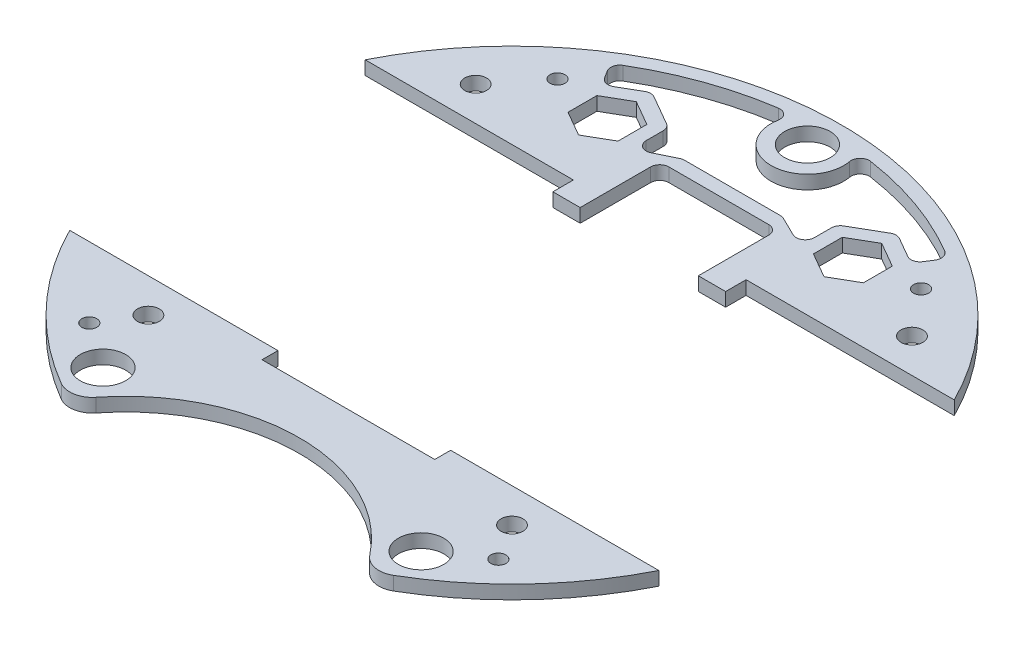
SolidWorks part; units mm, degrees
material "Acrylic (Medium-high impact)"
ref_plane "Front Plane" through (0, 0, 0) normal (0, 0, 1) x (1, 0, 0)
ref_plane "Top Plane" through (0, 0, 0) normal (0, 1, 0) x (1, 0, 0)
ref_plane "Right Plane" through (0, 0, 0) normal (1, 0, 0) x (0, 0, -1)
sketch "Sketch1" plane through (0, 0, 0) normal (0, 1, 0) x (1, 0, 0)
  line L0 (0, -85) -> (-32.4891, -64.8129) construction
  line L1 (0, -85) -> (0, 0) construction
  arc A0 (36.5434, -62.6165) -> (-36.5434, -62.6165) centre (0, 0) ccw
  arc A1 (30.0898, -61.3851) -> (-30.0898, -61.3851) centre (0, -85) ccw
  arc A2 (-30.0898, -61.3851) -> (-36.5434, -62.6165) centre (-34.0231, -58.2982) cw
  arc A3 (36.5434, -62.6165) -> (30.0898, -61.3851) centre (34.0231, -58.2982) cw
  dimension "D1" = 145
  dimension "D2" = 76.5
  dimension "D4" = 5
  dimension "D3" = 85
extrude "Boss-Extrude1" add sketch "Sketch1" along normal blind 3
sketch "solenoid placement" plane through (0, 3, 0) normal (0, 1, 0) x (1, 0, 0)
  line L4 (-19, -36) -> (19, -36)
  line L5 (-19, 28) -> (-19, -36)
  line L6 (19, 28) -> (-19, 28)
  line L7 (19, -36) -> (19, 28)
  line L8 (-19, -36) -> (19, -36)
  line L9 (-19, 28) -> (-19, -36)
  line L10 (19, 28) -> (-19, 28)
  line L11 (19, -36) -> (19, 28)
  dimension "D1" = 0
extrude "Cut-Extrude1" cut sketch "solenoid placement" against normal through all
sketch "Sketch4" plane through (0, 3, 0) normal (0, 1, 0) x (1, 0, 0)
  line L8 (13, 28) -> (13, 43.5)
  line L9 (-13, 28) -> (13, 28)
  line L10 (-13, 43.5) -> (-13, 28)
  line L11 (11, 45.5) -> (-11, 45.5)
  line L28 (13, 28) -> (13, 43.5)
  line L29 (-13, 28) -> (13, 28)
  line L30 (-13, 43.5) -> (-13, 28)
  line L31 (11, 45.5) -> (-11, 45.5)
  arc A4 (-11, 45.5) -> (-13, 43.5) centre (-11, 43.5) ccw
  arc A5 (13, 43.5) -> (11, 45.5) centre (11, 43.5) ccw
  arc A14 (-11, 45.5) -> (-13, 43.5) centre (-11, 43.5) ccw
  arc A15 (13, 43.5) -> (11, 45.5) centre (11, 43.5) ccw
  dimension "D1" = 0
extrude "Cut-Extrude4" cut sketch "Sketch4" against normal through all
sketch "Sketch5" plane through (0, 3, 0) normal (0, 1, 0) x (1, 0, 0)
  line L12 (-21.5, 51.1754) -> (-27, 54.3509)
  line L13 (-27, 54.3509) -> (-32.5, 51.1754)
  line L14 (-32.5, 51.1754) -> (-32.5, 44.8246)
  line L15 (-32.5, 44.8246) -> (-27, 41.6491)
  line L16 (-27, 41.6491) -> (-21.5, 44.8246)
  line L17 (-21.5, 44.8246) -> (-21.5, 51.1754)
  line L18 (-21.5, 51.1754) -> (-27, 54.3509)
  line L19 (-27, 54.3509) -> (-32.5, 51.1754)
  line L20 (-32.5, 51.1754) -> (-32.5, 44.8246)
  line L21 (-32.5, 44.8246) -> (-27, 41.6491)
  line L22 (-27, 41.6491) -> (-21.5, 44.8246)
  line L23 (-21.5, 44.8246) -> (-21.5, 51.1754)
  line L24 (21.5, 51.1754) -> (21.5, 44.8246)
  line L25 (21.5, 44.8246) -> (27, 41.6491)
  line L26 (27, 41.6491) -> (32.5, 44.8246)
  line L27 (32.5, 44.8246) -> (32.5, 51.1754)
  line L28 (32.5, 51.1754) -> (27, 54.3509)
  line L29 (27, 54.3509) -> (21.5, 51.1754)
  line L42 (21.5, 51.1754) -> (21.5, 44.8246)
  line L43 (21.5, 44.8246) -> (27, 41.6491)
  line L44 (27, 41.6491) -> (32.5, 44.8246)
  line L45 (32.5, 44.8246) -> (32.5, 51.1754)
  line L46 (32.5, 51.1754) -> (27, 54.3509)
  line L47 (27, 54.3509) -> (21.5, 51.1754)
  dimension "D1" = 0
  dimension "D2" = 0
extrude "Cut-Extrude5" cut sketch "Sketch5" against normal through all
sketch "Sketch6" plane through (0, 3, 0) normal (0, 1, 0) x (1, 0, 0)
  circle A1 centre (40, -40) radius 2.4
  circle A2 centre (40, -40) radius 2.4
  circle A3 centre (-40, -40) radius 2.4
  circle A4 centre (-40, -40) radius 2.4
  circle A5 centre (48, 40) radius 2.4
  circle A6 centre (48, 40) radius 2.4
  circle A7 centre (-48, 40) radius 2.4
  circle A8 centre (-48, 40) radius 2.4
  dimension "D1" = 0
  dimension "D2" = 0
  dimension "D3" = 0
  dimension "D4" = 0
extrude "Cut-Extrude6" cut sketch "Sketch6" against normal through all
sketch "Sketch3" plane through (0, 3, 0) normal (0, 1, 0) x (1, 0, 0)
  line L0 (-19, 28) -> (-19, 32.5)
  line L1 (72.5, -32.5) -> (-72.5, -32.5)
  line L2 (72.5, -32.5) -> (72.5, 32.5)
  line L3 (72.5, 32.5) -> (19, 32.5)
  line L4 (-72.5, -32.5) -> (-72.5, 32.5)
  line L5 (72.5, -32.5) -> (-72.5, 32.5) construction
  line L6 (72.5, 32.5) -> (-72.5, -32.5) construction
  line L7 (-19, 28) -> (19, 28)
  line L8 (19, 28) -> (19, 32.5)
  line L9 (-19, 32.5) -> (-72.5, 32.5)
  line L10 (-19, 28) -> (-19, -36) construction
  line L11 (-13, 28) -> (-19, 28) construction
  arc A0 (36.5434, -62.6165) -> (-36.5434, -62.6165) centre (0, 0) ccw construction
  point P0 (0, 0)
  dimension "D1" = 65
extrude "Cut-Extrude3" cut sketch "Sketch3" against normal through all
sketch "Sketch7" plane through (0, 3, 0) normal (0, 1, 0) x (1, 0, 0)
  circle A1 centre (35, -55) radius 5
  circle A2 centre (35, -55) radius 5
  circle A3 centre (-35, -55) radius 5
  circle A4 centre (-35, -55) radius 5
  dimension "D1" = 0
  dimension "D2" = 0
extrude "Cut-Extrude7" cut sketch "Sketch7" against normal through all
sketch "Sketch8" plane through (0, 3, 0) normal (0, -1, 0) x (1, 0, 0)
  circle A1 centre (0, -65) radius 5
  circle A2 centre (0, -65) radius 5
  dimension "D1" = 0
extrude "Cut-Extrude9" cut sketch "Sketch8" along normal through all
sketch "Sketch9" plane through (0, 3, 0) normal (0, 1, 0) x (1, 0, 0)
  line L0 (0, 0) -> (0, -21.5516) construction
  circle A0 centre (45, -48) radius 1.65
  circle A1 centre (-45, -48) radius 1.65
  circle A2 centre (40, 50) radius 1.65
  circle A3 centre (-40, 50) radius 1.65
  dimension "D3" = 3.3
  dimension "D1" = 45
  dimension "D2" = 48
  dimension "D4" = 40
  dimension "D5" = 50
extrude "Cut-Extrude10" cut sketch "Sketch9" against normal through all
sketch "Sketch10" plane through (0, 0, 0) normal (0, -1, 0) x (1, 0, 0)
  line L21 (-18.5, -44.8246) -> (-18.5, -52.9075)
  line L22 (-18.5, -52.9075) -> (-27, -57.815)
  line L23 (-27, -57.815) -> (-34, -53.7735)
  line L24 (-18.5, -48.0319) -> (-18.5, -51.7528)
  line L25 (-19.5, -53.4848) -> (-26, -57.2376)
  line L26 (-28, -57.2376) -> (-32.3362, -54.7341)
  line L31 (15.6199, -46.236) -> (11.4164, -48.2959)
  line L32 (11, -48.5) -> (-11, -48.5)
  line L33 (34, -53.7735) -> (27, -57.815)
  line L34 (27, -57.815) -> (18.5, -52.9075)
  line L35 (18.5, -52.9075) -> (18.5, -44.8246)
  line L36 (32.3362, -54.7341) -> (28, -57.2376)
  line L37 (26, -57.2376) -> (19.5, -53.4848)
  line L38 (18.5, -51.7528) -> (18.5, -48.0319)
  line L39 (10.5363, -48.5) -> (-10.5363, -48.5)
  line L40 (35.0267, -55.3973) -> (36.0573, -57.0273)
  line L41 (-11.4164, -48.2959) -> (-15.6199, -46.236)
  line L42 (-35.0267, -55.3973) -> (-36.0573, -57.0273)
  arc A21 (-62.1257, -31.1552) -> (62.1257, -31.1552) centre (0, 0) ccw
  arc A22 (-35.3852, -59.8175) -> (-10.1321, -68.7575) centre (0, 0) ccw
  arc A23 (10.1321, -68.7575) -> (35.3852, -59.8175) centre (0, 0) ccw
  circle A24 centre (0, -65) radius 8
  arc A25 (7.8724, -66.4231) -> (-7.8724, -66.4231) centre (0, -65) ccw
  arc A26 (-7.8724, -66.4231) -> (-10.1321, -68.7575) centre (-9.8405, -66.7788) cw
  arc A27 (7.8724, -66.4231) -> (10.1321, -68.7575) centre (9.8405, -66.7788) ccw
  arc A28 (36.0573, -57.0273) -> (35.3852, -59.8175) centre (34.3669, -58.0962) cw
  arc A29 (32.3362, -54.7341) -> (35.0267, -55.3973) centre (33.3362, -56.4661) cw
  arc A30 (28, -57.2376) -> (26, -57.2376) centre (27, -55.5056) cw
  arc A31 (19.5, -53.4848) -> (18.5, -51.7528) centre (20.5, -51.7528) cw
  arc A32 (18.5, -48.0319) -> (15.6199, -46.236) centre (16.5, -48.0319) ccw
  arc A33 (10.5363, -48.5) -> (11.4164, -48.2959) centre (10.5363, -46.5) ccw
  arc A34 (-10.5363, -48.5) -> (-11.4164, -48.2959) centre (-10.5363, -46.5) cw
  arc A35 (-18.5, -48.0319) -> (-15.6199, -46.236) centre (-16.5, -48.0319) cw
  arc A36 (-18.5, -51.7528) -> (-19.5, -53.4848) centre (-20.5, -51.7528) cw
  arc A37 (-26, -57.2376) -> (-28, -57.2376) centre (-27, -55.5056) cw
  arc A38 (-32.3362, -54.7341) -> (-35.0267, -55.3973) centre (-33.3362, -56.4661) ccw
  arc A39 (-36.0573, -57.0273) -> (-35.3852, -59.8175) centre (-34.3669, -58.0962) ccw
  point P23 (6.8312, -69.1635)
  dimension "D6" = 2
  dimension "D1" = 3
  dimension "D2" = 3
  dimension "D3" = 3
  dimension "D4" = 3
  dimension "D5" = 3
extrude "Cut-Extrude12" cut sketch "Sketch10" against normal through all contours L42 A39 A22 A26 A25 A27 A23 A28 L40 A29 L36 A30 L37 A31 L38 A32 L31 A33 L39 A34 L41 A35 L24 A36 L25 A37 L26 A38 region at (-17.155, 0, -46.9815) region at (-18.7098, 0, -52.7863) region at (-27, 0, -57.5727) region at (18.7098, 0, -52.7863) region at (27, 0, -57.5727)
equation "\"smallPulleyTeeth\"= 30"
equation "\"largePulleyTeeth\"= 30"
equation "\"eighthThick\"= 3.0mm"
equation "\"sixteenthThick\" = 1.7mm"
equation "\"quarterThick\"=6.0mm"
equation "\"OD\" = 145mm"
equation "\"puckAngle\" = 60.5deg"
equation "\"D1@Sketch1\"=\"OD\""
equation "\"puckDiam\" = 76.5mm"
equation "\"D2@Sketch1\"=\"puckDiam\""
equation "\"D1@Boss-Extrude1\"=\"eighthThick\""
equation "\"axlePress\" = 5.9mm"
equation "\"press\" = 0.2mm"
equation "\"wheelClear\" = 0.3mm"
equation "\"10-32clear\" = 4.8mm"
equation "\"6-32clear\" = 3.3mm"
equation "\"8-32clear\" = 4.0mm"
equation "\"wheelHeight\" = 22mm"
equation "\"wheelWell\" = 65mm"
equation "\"D1@Sketch3\"=\"wheelWell\""
equation "\"puckDist\" = 85mm"
equation "\"scoopFillet\" = 5mm"
equation "\"4-40clear\" = 3.0mm"
equation "\"D3@Sketch1\"=\"puckDist\""
equation "\"D4@Sketch1\"=\"scoopFillet\""
equation "\"D3@Sketch9\"=\"6-32clear\""
